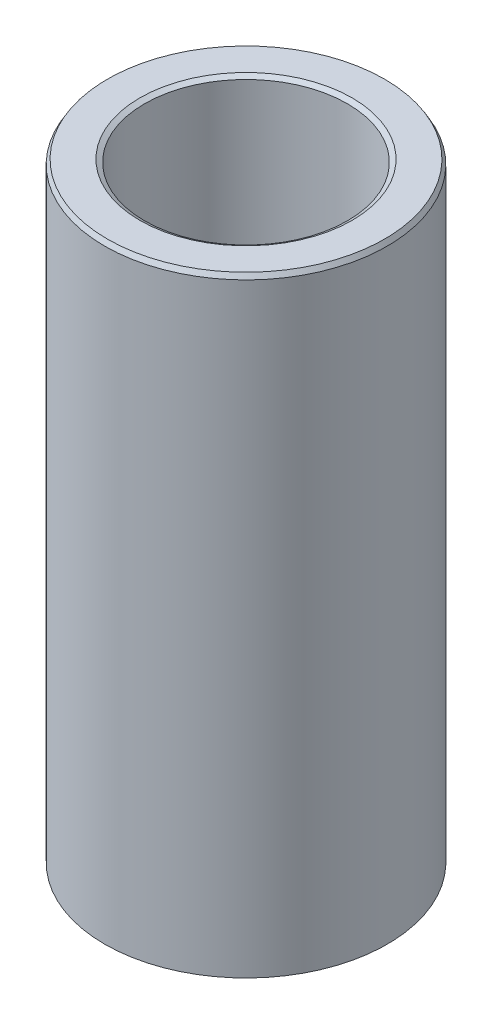
SolidWorks part; units mm, degrees
ref_plane "Front Plane" through (0, 0, 0) normal (0, 0, 1) x (1, 0, 0)
ref_plane "Top Plane" through (0, 0, 0) normal (0, 1, 0) x (1, 0, 0)
ref_plane "Right Plane" through (0, 0, 0) normal (1, 0, 0) x (0, 0, -1)
sketch "Sketch1" plane through (0, 0, 0) normal (0, 1, 0) x (1, 0, 0)
  circle A0 centre (0, 0) radius 42.5
  dimension "SLEEVE_OD" = 85
extrude "Boss-Extrude1" add sketch "Sketch1" along normal blind 184.0808
sketch "Sketch2" plane through (0, 0, 0) normal (0, 1, 0) x (1, 0, 0)
  circle A0 centre (0, 0) radius 30.5049
  dimension "BORE_D" = 61.0097
extrude "Cut-Extrude1" cut sketch "Sketch2" along normal through all
chamfer "Chamfer1" distance 1.4202 angle 30 4 edges at (0, 184.0808, 30.5049) (0, 0, 30.5049) (0, 0, 42.5) (0, 184.0808, 42.5) first distance on face at (0, 184.0808, 30.5049) first distance on face at (0, 0, 30.5049) first distance on face at (0, 184.0808, 42.5)
